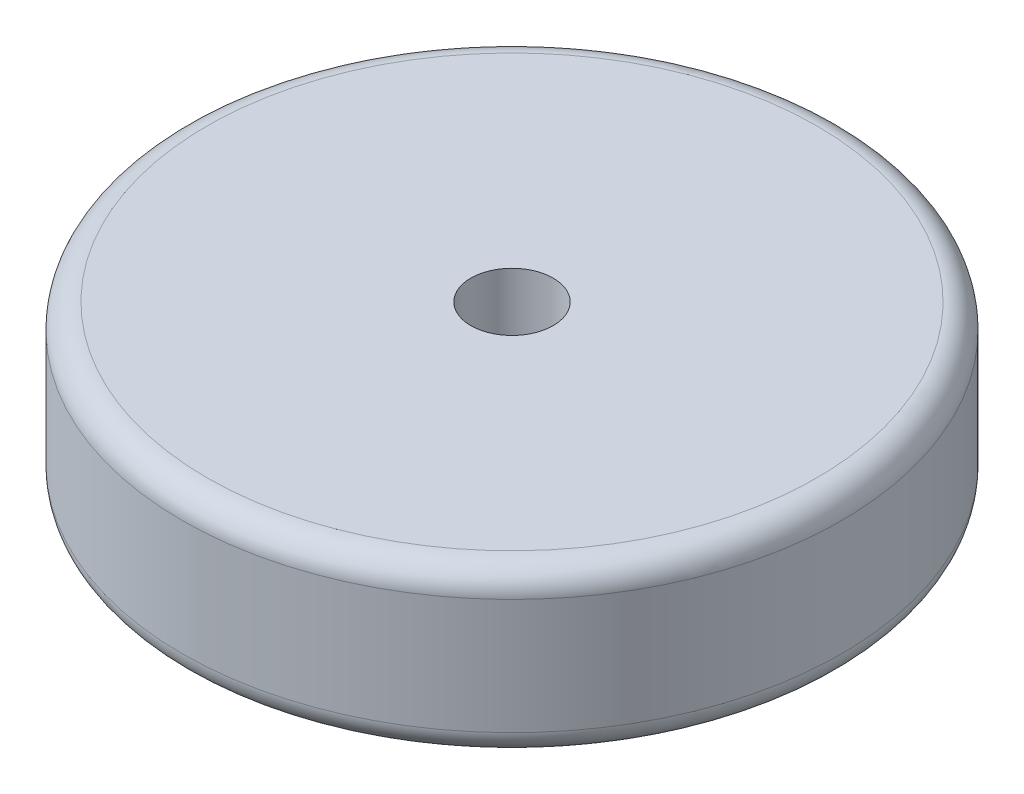
SolidWorks part; units mm, degrees
ref_plane "前基準面" through (0, 0, 0) normal (0, 0, 1) x (1, 0, 0)
ref_plane "上基準面" through (0, 0, 0) normal (0, 1, 0) x (1, 0, 0)
ref_plane "右基準面" through (0, 0, 0) normal (1, 0, 0) x (0, 0, -1)
sketch "草圖1" plane through (0, 0, 0) normal (0, 1, 0) x (1, 0, 0)
  circle A0 centre (0, 0) radius 40
  circle A1 centre (0, 0) radius 5
  dimension "D1" = 80
  dimension "D2" = 10
extrude "填料-伸長1" add sketch "草圖1" along normal blind 20
fillet "圓角1" radius 3 2 edges at (0, 0, 40) (0, 20, 40)
